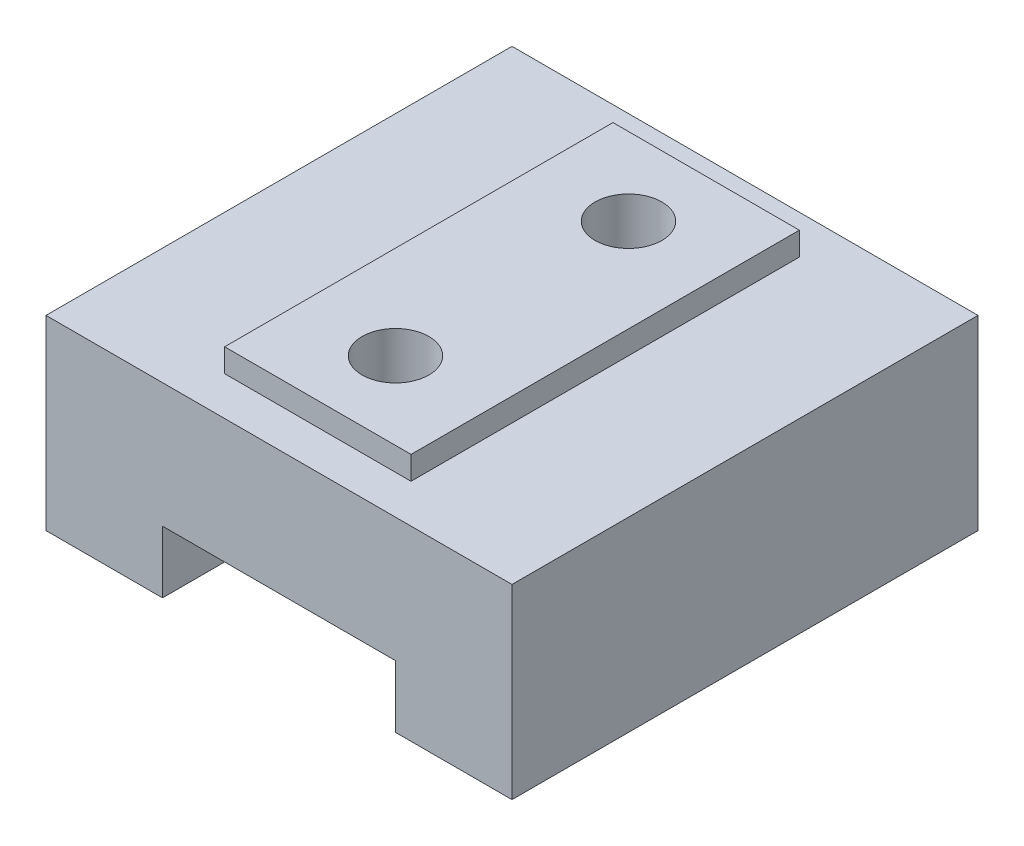
SolidWorks part; units mm, degrees
ref_plane "Front Plane" through (0, 0, 0) normal (0, 0, 1) x (1, 0, 0)
ref_plane "Top Plane" through (0, 0, 0) normal (0, 1, 0) x (1, 0, 0)
ref_plane "Right Plane" through (0, 0, 0) normal (1, 0, 0) x (0, 0, -1)
sketch "Sketch1" plane through (0, 0, 0) normal (0, 1, 0) x (1, 0, 0)
  line L1 (15, -15) -> (-15, -15)
  line L2 (15, -15) -> (15, 15)
  line L3 (15, 15) -> (-15, 15)
  line L4 (-15, -15) -> (-15, 15)
  line L5 (15, -15) -> (-15, 15) construction
  line L6 (15, 15) -> (-15, -15) construction
  point P0 (0, 0)
  dimension "D1" = 30
extrude "Boss-Extrude1" add sketch "Sketch1" along normal blind 12
sketch "Sketch2" plane through (0, 12, 0) normal (0, 1, 0) x (1, 0, 0)
  line L0 (-15, 0) -> (15, 0) construction
  line L1 (-15, 15) -> (-15, -15) construction
  line L2 (15, -15) -> (15, 15) construction
  line L3 (0, 12.5) -> (0, -12.5) construction
  line L4 (6, 12.5) -> (-6, 12.5)
  line L5 (6, 12.5) -> (6, -12.5)
  line L6 (6, -12.5) -> (-6, -12.5)
  line L7 (-6, 12.5) -> (-6, -12.5)
  circle A0 centre (0, -7.5) radius 2.15
  circle A1 centre (0, 7.5) radius 2.15
  point P17 (0, 0)
  dimension "D3" = 4.3
  dimension "D1" = 12
  dimension "D2" = 25
  dimension "D4" = 5
  dimension "D5" = 15
extrude "Cut-Extrude1" cut sketch "Sketch2" against normal through all contours A0 | A1 region at (0, 12, 7.5)
extrude "Boss-Extrude2" add sketch "Sketch2<3>" along normal blind 1.5
sketch "Sketch2<3>" plane through (0, 12, 0) normal (0, 1, 0) x (1, 0, 0) same geometry as "Sketch2"
sketch "Sketch3" plane through (0, 0, 0) normal (0, -1, 0) x (1, 0, 0)
  line L0 (-15, 15) -> (15, 15) construction
  line L1 (-7.5, 15) -> (7.5, 15)
  line L2 (-7.5, 15) -> (-7.5, -15)
  line L3 (-7.5, -15) -> (7.5, -15)
  line L4 (7.5, 15) -> (7.5, -15)
  line L5 (-15, -15) -> (-15, 15) construction
  point P6 (0, 15)
  point P7 (0, 15)
  point P10 (-15, 0)
  point P11 (-7.5, 0)
  dimension "D1" = 30
  dimension "D2" = 15
extrude "Cut-Extrude2" cut sketch "Sketch3" against normal blind 4
